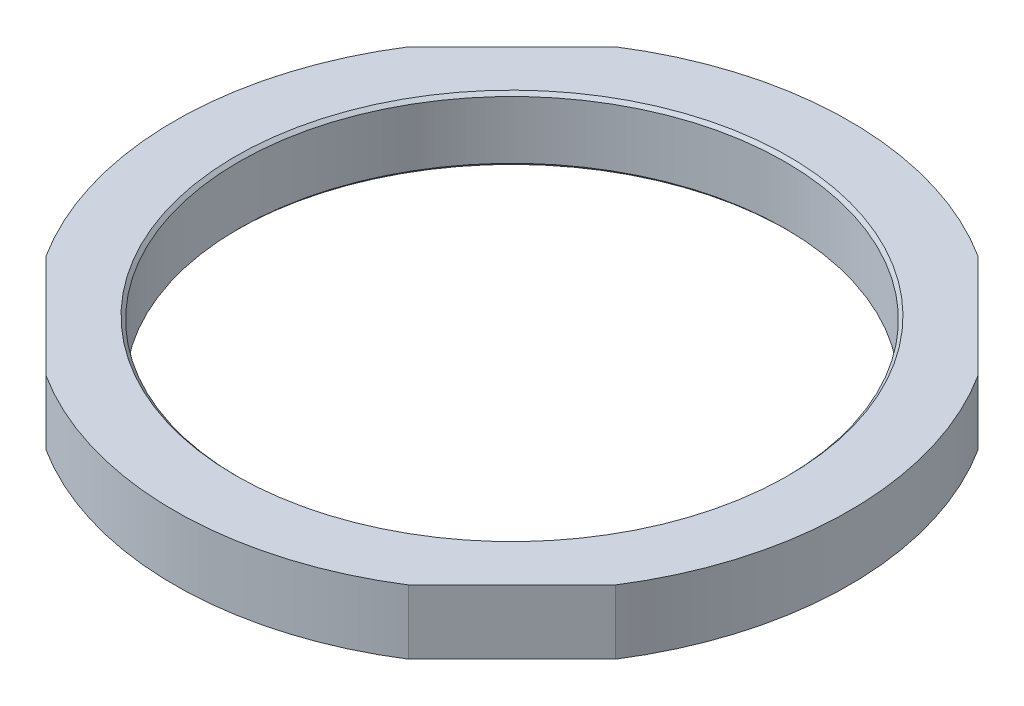
SolidWorks part; units mm, degrees
material "Ceramic Porcelain"
ref_plane "Front Plane" through (0, 0, 0) normal (0, 0, 1) x (1, 0, 0)
ref_plane "Top Plane" through (0, 0, 0) normal (0, 1, 0) x (1, 0, 0)
ref_plane "Right Plane" through (0, 0, 0) normal (1, 0, 0) x (0, 0, -1)
ref_axis "CentralAxis" through (0, 1.1, 0) along (0, -1, 0)
sketch "BaseS" plane through (0, 0, 0) normal (0, 1, 0) x (1, 0, 0)
  circle A0 centre (0, 0) radius 17
  circle A1 centre (0, 0) radius 21
  dimension "InnerDiameter" = 34
  dimension "OuterDiameter" = 42
extrude "Base" add sketch "BaseS" along normal mid plane 4
sketch "FlatCutS" plane through (0, 0, 0) normal (0, 1, 0) x (1, 0, 0)
  line L0 (11.2747, 17.7167) -> (17.7167, 11.2747)
  line L1 (0, 0) -> (14.4957, 14.4957) construction
  line L2 (0, 0) -> (21, 0) construction
  line L3 (0, 0) -> (-14.8492, 14.8492) construction
  line L4 (14.4957, 14.4957) -> (14.8492, 14.8492) construction
  circle A0 centre (0, 0) radius 21 construction
  arc A1 (17.7167, 11.2747) -> (11.2747, 17.7167) centre (0, 0) ccw
  dimension "Angle" = 45
  dimension "RefCutWidth" = 41
  dimension "CutWidth" = 0.5
extrude "FlatCut" cut sketch "FlatCutS" against normal through all both and the other way through all
pattern_circular "FCCirPattern" count 4 over 360 about axis through (0, 1.1, 0) along (0, -1, 0) of "FlatCut"
chamfer "BaseChamfer" distance 0.2 angle 45 2 edges at (0, -2, 17) (0, 2, 17)
